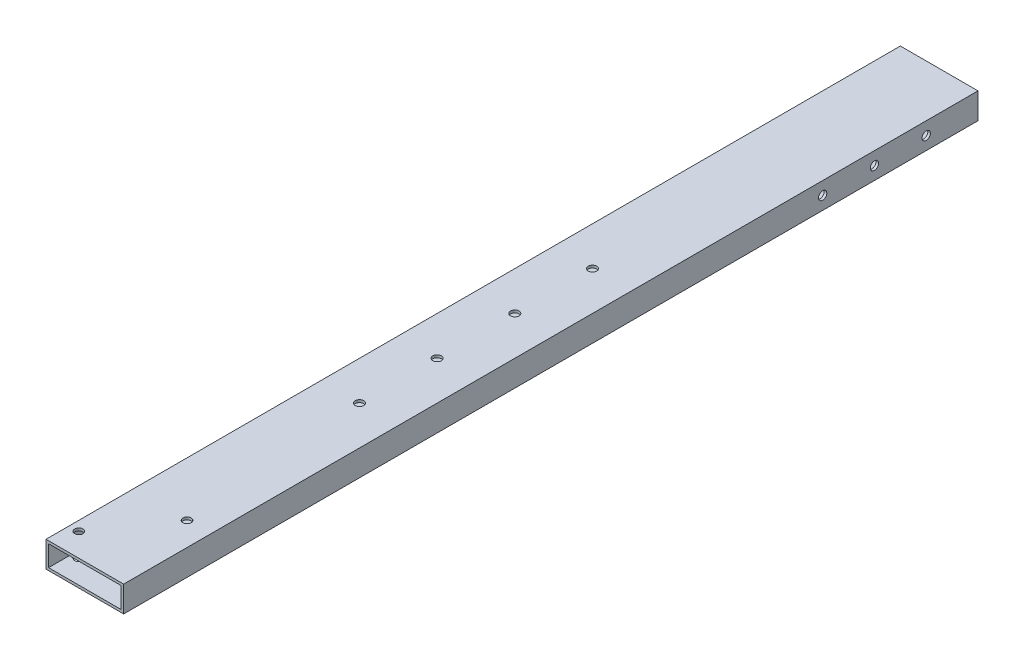
SolidWorks part; units mm, degrees
material "6061 合金"
ref_plane "前视基准面" through (0, 0, 0) normal (0, 0, 1) x (1, 0, 0)
ref_plane "上视基准面" through (0, 0, 0) normal (0, 1, 0) x (1, 0, 0)
ref_plane "右视基准面" through (0, 0, 0) normal (1, 0, 0) x (0, 0, -1)
other "Configuration Table"
sketch "草图1" plane through (0, 0, 0) normal (0, 0, 1) x (1, 0, 0)
  line L1 (-15, 5) -> (15, 5)
  line L2 (-15, 5) -> (-15, -5)
  line L3 (-15, -5) -> (15, -5)
  line L4 (15, 5) -> (15, -5)
  line L5 (-15, 5) -> (15, -5) construction
  line L6 (-15, -5) -> (15, 5) construction
  line L7 (-13, 3) -> (13, 3)
  line L8 (-13, 3) -> (-13, -3)
  line L9 (-13, -3) -> (13, -3)
  line L10 (13, 3) -> (13, -3)
  line L11 (-13, 3) -> (13, -3) construction
  line L12 (-13, -3) -> (13, 3) construction
  point P0 (0, 0)
  point P6 (0, 0)
  dimension "2" = 2
  dimension "D2" = 2
  dimension "D3" = 10
  dimension "D4" = 30
extrude "凸台-拉伸1" add sketch "草图1" along normal blind 330
sketch "草图2" plane through (0, 5, 0) normal (0, 1, 0) x (1, 0, 0)
  line L0 (-15, -330) -> (-15, 0) construction
  line L1 (15, -330) -> (-15, -330) construction
  circle A0 centre (-11.3, -321) radius 1.6
  dimension "D1" = 3.2
  dimension "D2" = 3.7
  dimension "D3" = 9
extrude "切除-拉伸1" cut sketch "草图2" against normal through all
sketch "草图3" plane through (0, 5, 0) normal (0, 1, 0) x (1, 0, 0)
  circle A0 centre (5.9073, -296.4254) radius 1.6
  circle A1 centre (5.9073, -296.4254) radius 2
  circle A2 centre (5.9073, -296.4254) radius 2 construction
  circle A3 centre (-11.3, -321) radius 2
  circle A4 centre (-11.3, -321) radius 2 construction
  circle A112 centre (0, -163.9123) radius 1.65
  circle A113 centre (0, -163.9123) radius 1.65
  circle A114 centre (0, -133.9123) radius 1.65
  circle A115 centre (0, -133.9123) radius 1.65
  circle A120 centre (0, -223.9123) radius 1.65
  circle A121 centre (0, -223.9123) radius 1.65
  circle A122 centre (0, -193.9123) radius 1.65
  circle A123 centre (0, -193.9123) radius 1.65
  dimension "D3" = 3.2
  dimension "D1" = 0
  dimension "D2" = 0
  dimension "D4" = 0
  dimension "D5" = 0
  dimension "D8" = 0
  dimension "D9" = 0
extrude "切除-拉伸2" cut sketch "草图3" against normal through all
sketch "草图4" plane through (-15, 0, 0) normal (-1, 0, 0) x (0, 0, 1)
  line L0 (20, 0) -> (40, 0) construction
  circle A0 centre (20, 0) radius 1.6
  circle A1 centre (40, 0) radius 1.6
  circle A2 centre (60, 0) radius 1.6
  dimension "D1" = 20
  dimension "D2" = 3.2
  dimension "D4" = 20
  dimension "D3" = 3
extrude "切除-拉伸3" cut sketch "草图4" against normal through all
sketch "草图5" plane through (0, 5, 0) normal (0, 1, 0) x (1, 0, 0)
  line L0 (0, -105) -> (0, -15) construction
  line L1 (-9, -105) -> (-9, -15)
  line L2 (9, -105) -> (9, -15)
  line L3 (15, -330) -> (15, 0) construction
  line L4 (15, 0) -> (-15, 0) construction
  arc A0 (-9, -105) -> (9, -105) centre (0, -105) ccw
  arc A1 (9, -15) -> (-9, -15) centre (0, -15) ccw
  point P2 (0, -60)
  dimension "D2" = 15
  dimension "D1" = 6
  dimension "D3" = 90
extrude "切除-拉伸4" [suppressed] cut sketch "草图5" against normal through all
sketch "草图6" plane through (0, 0, 0) normal (0, 0, -1) x (-1, 0, 0)
  line L0 (-15, 5) -> (15, 5) construction
  line L1 (-14, 4) -> (14, 4)
  line L2 (-14, 4) -> (-14, -4)
  line L3 (-14, -4) -> (14, -4)
  line L4 (14, 4) -> (14, -4)
  line L5 (15, 5) -> (15, -5) construction
  line L6 (-15, -5) -> (-15, 5) construction
  line L7 (15, -5) -> (-15, -5) construction
  dimension "D1" = 1
  dimension "D2" = 1
  dimension "D3" = 1
  dimension "D4" = 1
extrude "切除-拉伸5" cut sketch "草图6" against normal blind 355
